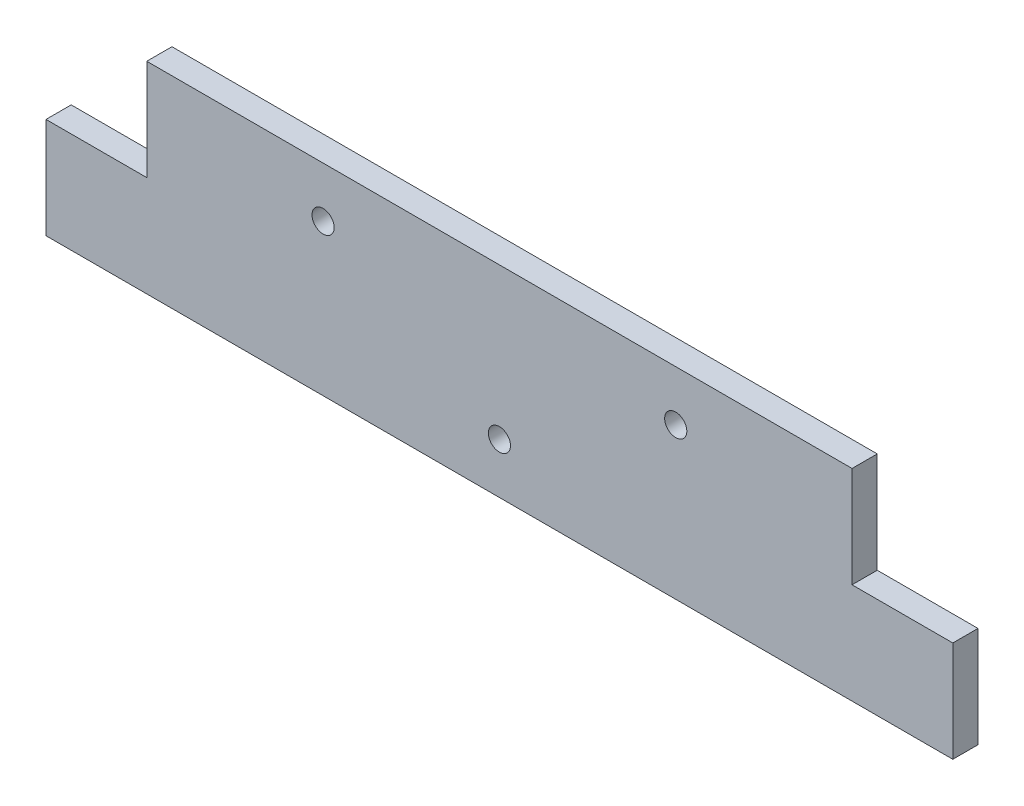
SolidWorks part; units mm, degrees
ref_plane "Płaszczyzna przednia" through (0, 0, 0) normal (0, 0, 1) x (1, 0, 0)
ref_plane "Płaszczyzna górna" through (0, 0, 0) normal (0, 1, 0) x (1, 0, 0)
ref_plane "Płaszczyzna prawa" through (0, 0, 0) normal (1, 0, 0) x (0, 0, -1)
sketch "Szkic1" plane through (0, 0, 0) normal (0, 0, 1) x (1, 0, 0)
  line L0 (0, -20) -> (-20, -20)
  line L2 (0, -20) -> (0, 0)
  line L3 (0, 0) -> (140, 0)
  line L4 (140, -20) -> (140, 0)
  line L7 (-20, -20) -> (-20, -40)
  line L8 (-20, -40) -> (160, -40)
  line L9 (160, -40) -> (160, -20)
  line L10 (160, -20) -> (140, -20)
  point P0 (0, 0)
  dimension "D1" = 180
  dimension "D2" = 40
  dimension "D3" = 20
  dimension "D4" = 20
  dimension "D5" = 20
extrude "Dodanie-wyciągnięcie1" add sketch "Szkic1" along normal blind 5
sketch "Szkic2" plane through (0, 0, 5) normal (0, 0, 1) x (1, 0, 0)
  line L0 (140, 0) -> (0, 0) construction
  line L1 (0, 0) -> (0, -20) construction
  line L2 (140, -20) -> (140, 0) construction
  circle A0 centre (35, -10) radius 2.2
  circle A2 centre (105, -10) radius 2.2
  dimension "D1" = 10
  dimension "D4" = 4.4
  dimension "D2" = 35
  dimension "D3" = 35
extrude "Wytnij-wyciągnięcie1" cut sketch "Szkic2" against normal blind 10
sketch "Szkic6" plane through (0, 0, 5) normal (0, 0, 1) x (1, 0, 0)
  line L0 (-20, -40) -> (160, -40) construction
  line L1 (160, -40) -> (160, -20) construction
  circle A0 centre (70, -30) radius 2.2
  dimension "D1" = 10
  dimension "D2" = 4.4
  dimension "D3" = 90
extrude "Wytnij-wyciągnięcie3" cut sketch "Szkic6" against normal through all
